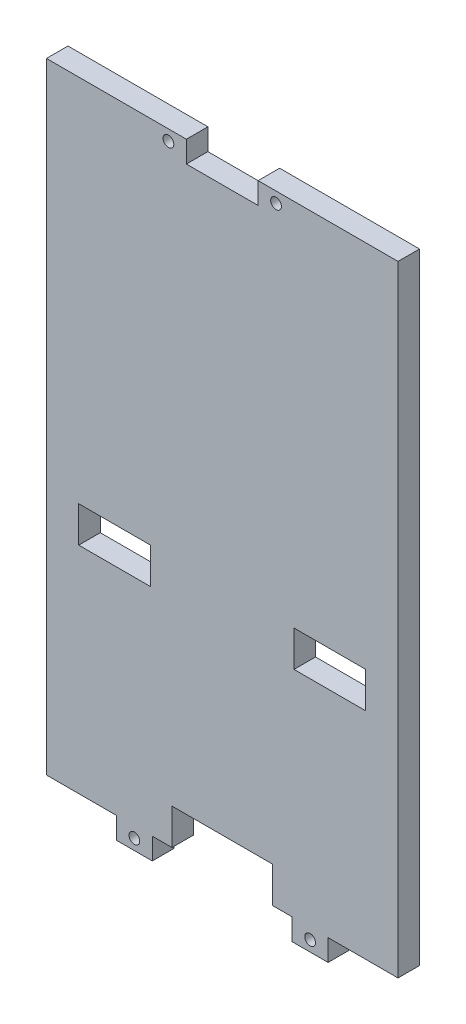
SolidWorks part; units mm, degrees
ref_plane "Plan de face" through (0, 0, 0) normal (0, 0, 1) x (1, 0, 0)
ref_plane "Plan de dessus" through (0, 0, 0) normal (0, 1, 0) x (1, 0, 0)
ref_plane "Plan de droite" through (0, 0, 0) normal (1, 0, 0) x (0, 0, -1)
sketch "Esquisse1" plane through (0, 0, 0) normal (0, 0, 1) x (1, 0, 0)
  line L0 (0, 176.8395) -> (0, -221.1538) construction
  line L1 (-49, 86.5) -> (49, 86.5)
  line L2 (-49, 86.5) -> (-49, -86.5)
  line L3 (-49, -86.5) -> (49, -86.5)
  line L4 (49, 86.5) -> (49, -86.5)
  line L5 (376.8436, 0) -> (-286.1998, 0) construction
  line L6 (-376.8436, 0) -> (286.1998, 0) construction
  line L7 (20, -16.5) -> (20, -26.5)
  line L8 (-40, -16.5) -> (-20, -16.5)
  line L9 (-40, -16.5) -> (-40, -26.5)
  line L10 (-40, -26.5) -> (-20, -26.5)
  line L11 (-20, -16.5) -> (-20, -26.5)
  line L12 (40, -26.5) -> (20, -26.5)
  line L13 (40, -16.5) -> (40, -26.5)
  line L14 (40, -16.5) -> (20, -16.5)
  dimension "D1" = 173
  dimension "D2" = 98
  dimension "D3" = 49
  dimension "D4" = 86.5
  dimension "D5" = 10
  dimension "D6" = 20
  dimension "D7" = 60
  dimension "D8" = 9
extrude "Boss.-Extru.1" add sketch "Esquisse1" along normal blind 6
sketch "Esquisse2" plane through (0, 0, 6) normal (0, 0, 1) x (1, 0, 0)
  line L1 (-49, -86.5) -> (49, -86.5) construction
  line L2 (29.5, -86.5) -> (19.5, -86.5)
  line L3 (29.5, -86.5) -> (29.5, -92.5)
  line L4 (29.5, -92.5) -> (19.5, -92.5)
  line L6 (154.6429, 0) -> (-167.6281, 0) construction
  line L7 (19.5, -86.5) -> (19.5, -92.5)
  line L8 (-49, 86.5) -> (-49, -86.5) construction
  line L9 (-19.5, -86.5) -> (-29.5, -86.5)
  line L10 (-19.5, -86.5) -> (-19.5, -92.5)
  line L11 (-19.5, -92.5) -> (-29.5, -92.5)
  line L12 (-29.5, -86.5) -> (-29.5, -92.5)
  dimension "D1" = 6
  dimension "D2" = 6
  dimension "D3" = 10
  dimension "D4" = 10
  dimension "D5" = 19.5
  dimension "D6" = 39
extrude "Boss.-Extru.2" add sketch "Esquisse2" against normal blind 6
sketch "Esquisse3" plane through (0, 0, 6) normal (0, 0, 1) x (1, 0, 0)
  line L0 (-49, 86.5) -> (-49, -86.5) construction
  line L1 (55.0284, -89.5) -> (-66.8616, -89.5) construction
  line L2 (84.5882, 83.5) -> (-34.9143, 83.5) construction
  line L3 (19.5, -92.5) -> (29.5, -92.5) construction
  line L4 (49, -86.5) -> (49, 86.5) construction
  line L5 (49, 86.5) -> (-49, 86.5) construction
  line L6 (-29.5, -86.5) -> (-29.5, -92.5) construction
  line L7 (19.5, -86.5) -> (19.5, -92.5) construction
  circle A0 centre (-15, 83.5) radius 1.5
  circle A1 centre (24.5, -89.5) radius 1.5
  circle A2 centre (-24.5, -89.5) radius 1.5
  circle A3 centre (15, 83.5) radius 1.5
  dimension "D1" = 3
  dimension "D2" = 3
  dimension "D3" = 34
  dimension "D4" = 34
  dimension "D7" = 3
  dimension "D8" = 3
  dimension "D9" = 5
  dimension "D10" = 5
  dimension "D5" = 3
  dimension "D6" = 3
extrude "Enlèv. mat.-Extru.1" cut sketch "Esquisse3" against normal blind 6
sketch "Esquisse4" plane through (0, 0, 6) normal (0, 0, 1) x (1, 0, 0)
  line L0 (49, 86.5) -> (-49, 86.5) construction
  line L1 (-10, 86.5) -> (10, 86.5)
  line L2 (-10, 86.5) -> (-10, 80.5)
  line L3 (-10, 80.5) -> (10, 80.5)
  line L4 (10, 86.5) -> (10, 80.5)
  line L5 (49, -86.5) -> (49, 86.5) construction
  line L6 (-19.5, -86.5) -> (19.5, -86.5) construction
  line L7 (-14, -86.5) -> (14, -86.5)
  line L8 (-14, -86.5) -> (-14, -76.5)
  line L9 (-14, -76.5) -> (14, -76.5)
  line L10 (14, -86.5) -> (14, -76.5)
  line L11 (-19.5, -92.5) -> (-19.5, -86.5) construction
  dimension "D1" = 6
  dimension "D2" = 20
  dimension "D3" = 39
  dimension "D4" = 10
  dimension "D5" = 28
  dimension "D6" = 5.5
extrude "Enlèv. mat.-Extru.2" cut sketch "Esquisse4" against normal blind 6
equation "\"D3@Esquisse1\"=\"D2@Esquisse1\"/2"
equation "\"D4@Esquisse1\"=\"D1@Esquisse1\"/2"
